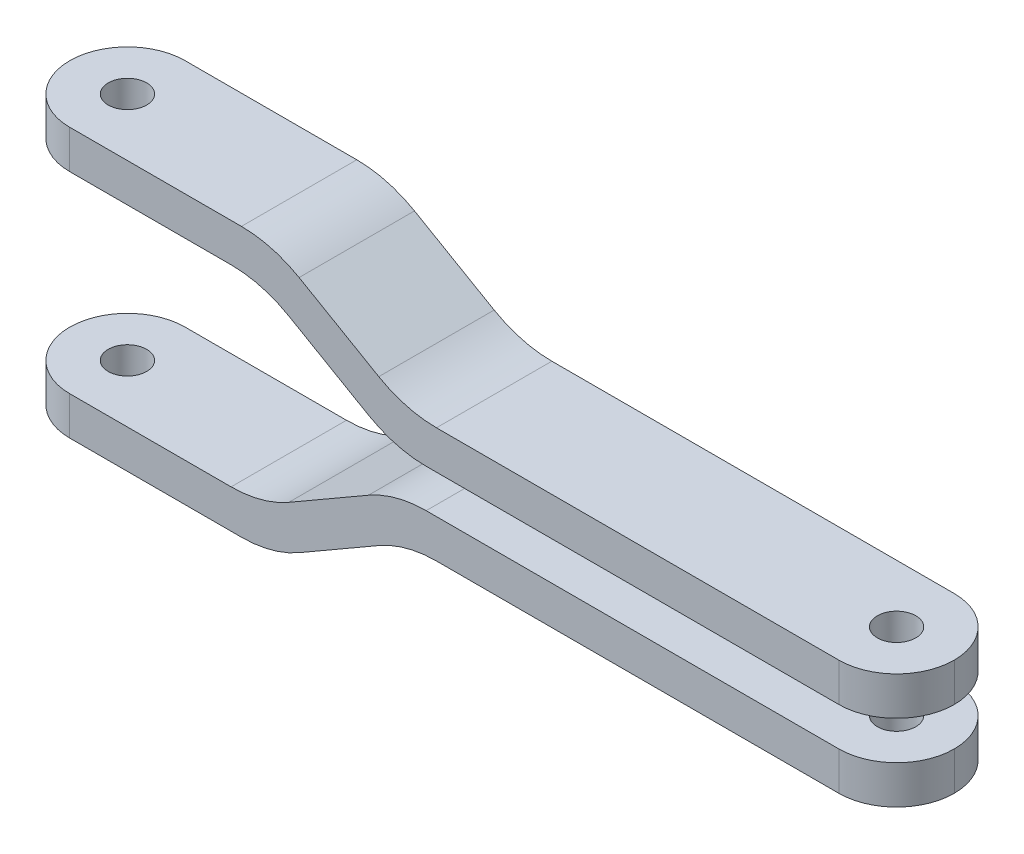
SolidWorks part; units mm, degrees
ref_plane "Alzado" through (0, 0, 0) normal (1, 0, 0) x (0, 1, 0)
ref_plane "Planta" through (0, 0, 0) normal (0, 0, 1) x (0, 1, 0)
ref_plane "Vista lateral" through (0, 0, 0) normal (0, 1, 0) x (-1, 0, 0)
sketch "Croquis1" plane through (0, 0, 0) normal (0, 1, 0) x (-1, 0, 0)
  line L0 (0, 0) -> (200, 0) construction
  line L1 (200, 0) -> (0, 0) construction
  circle A0 centre (0, 0) radius 5
  circle A1 centre (200, 0) radius 5
  dimension "D2" = 10
  dimension "D1" = 200
sketch "Croquis3" plane through (0, 0, 0) normal (0, 0, 1) x (0, 1, 0)
  line L1 (0, 0) -> (0, 200) construction
  line L2 (-25, 215) -> (-25, 150)
  line L3 (-25, 150) -> (-5, 115.359)
  line L4 (-5, 115.359) -> (-5, -15)
  line L5 (-25, 215) -> (-35, 215)
  line L6 (-35, 215) -> (-35, 147.3205)
  line L7 (-35, 147.3205) -> (-15, 112.6795)
  line L8 (-15, 112.6795) -> (-15, -15)
  line L9 (-5, -15) -> (-15, -15)
  point P10 (0, 200)
  point P11 (0, 0)
  point P14 (-14.5, 152.7381)
  point P15 (20.5, 207.0921)
  point P18 (0, 0)
  dimension "D1" = 10
  dimension "D2" = 10
  dimension "D3" = 15
  dimension "D6" = 30
  dimension "D7" = 15
  dimension "D8" = 10
  dimension "D10" = 10
  dimension "D4" = 50
  dimension "D5" = 50
extrude "Saliente-Extruir1" add sketch "Croquis3" along normal mid plane 30
fillet "Redondeo3" radius 15 4 edges at (15, -10, 15) (15, -10, -15) (-215, -30, -15) (-215, -30, 15)
fillet "Redondeo2" radius 30 4 edges at (-112.6795, -15, 0) (-147.3205, -35, 0) (-150, -25, 0) (-115.359, -5, 0)
sketch "Croquis4" plane through (0, 0, 0) normal (0, 1, 0) x (-1, 0, 0)
  circle A0 centre (0, 0) radius 5
  circle A1 centre (200, 0) radius 5
  circle A3 centre (200, 0) radius 5 construction
  dimension "D1" = 10
extrude "Cortar-Extruir1" cut sketch "Croquis4" against normal up to next
mirror "Simetría2" about plane through (0, 0, 0) normal (0, 1, 0) of bodies 102
equation "\"D8@Croquis3\"=\"D1@Croquis3\""
equation "\"L2\"= 200"
equation "\"esp\"= 10"
equation "\"ancho\"= 30"
equation "\"D1@Croquis1\"=\"L2\""
equation "\"D1@Saliente-Extruir1\"=\"ancho\""
equation "\"D1@Croquis4\"=\"esp\""
equation "\"D1@Redondeo3\" = \"ancho\" / 2"
equation "\"D1@Croquis3\"=\"esp\""
equation "\"D2@Croquis3\"=\"esp\""
equation "\"D7@Croquis3\"=\"ancho\"/2"
equation "\"D4@Croquis3\"=\"L2\"/4"
equation "\"D3@Croquis3\"=\"ancho\"/2"
equation "\"D10@Croquis3\"=\"esp\""
equation "\"ancho_total_L1\"= 45"
equation "\"D5@Croquis3\"=\"ancho_total_L1\"+5"
equation "\"ang_L2\"= 30"
equation "\"D6@Croquis3\"=\"ang_L2\""
